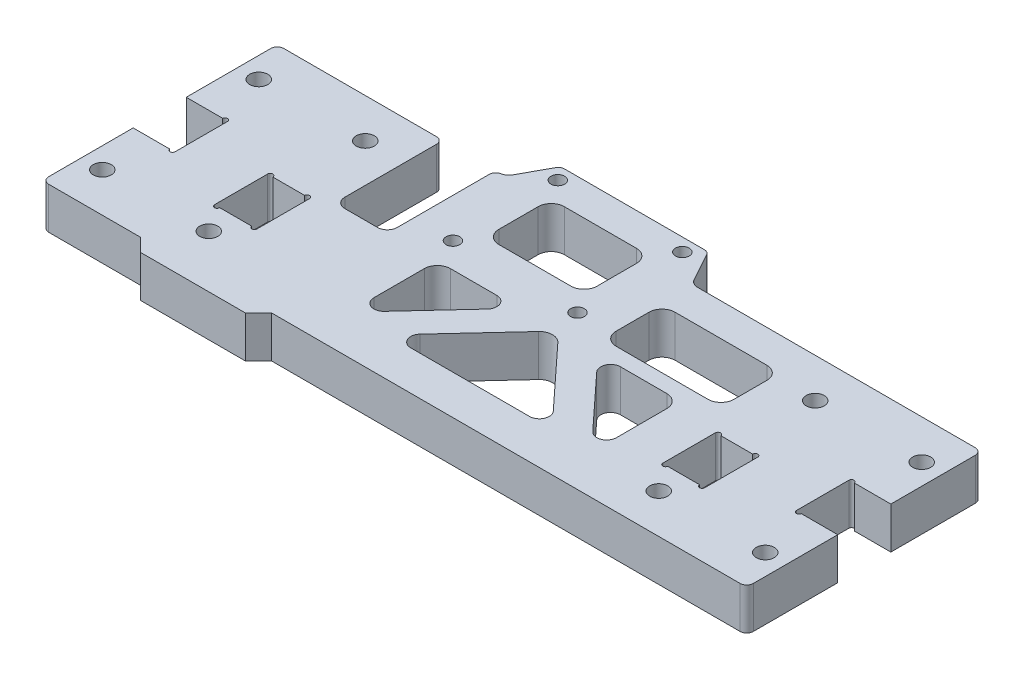
SolidWorks part; units mm, degrees
material "6061 Alloy"
ref_plane "Front Plane" through (0, 0, 0) normal (0, 0, 1) x (1, 0, 0)
ref_plane "Top Plane" through (0, 0, 0) normal (0, 1, 0) x (1, 0, 0)
ref_plane "Right Plane" through (0, 0, 0) normal (1, 0, 0) x (0, 0, -1)
sketch "Sketch1" plane through (0, 0, 0) normal (0, 1, 0) x (1, 0, 0)
  line L0 (107.5, 76.65) -> (107.5, 0) construction
  line L6 (32.7004, 36.1) -> (32.7004, 19.9)
  line L8 (45.6, 36) -> (45.6, 20)
  line L13 (0, 71.75) -> (69.5, 71.75)
  line L14 (69.5, 71.75) -> (75.5, 82.75)
  line L15 (75.5, 82.75) -> (120.5, 82.75)
  line L16 (120.5, 82.75) -> (126.5, 71.75)
  line L17 (126.5, 71.75) -> (215, 71.75)
  line L18 (32.7004, 28) -> (45.6, 28) construction
  line L19 (34.3004, 36.1) -> (44.0063, 36.1)
  line L20 (34.3004, 19.9) -> (44.0063, 19.9)
  line L21 (182.2996, 36.1) -> (182.2996, 19.9)
  line L22 (180.6996, 36.1) -> (170.9937, 36.1)
  line L23 (169.4, 36) -> (169.4, 20)
  line L24 (180.6996, 19.9) -> (170.9937, 19.9)
  line L25 (12.7, 35.875) -> (0, 35.875) construction
  line L29 (12.7, 43.975) -> (12.7, 27.775)
  line L30 (11.1189, 43.975) -> (0, 43.975)
  line L31 (11.1189, 27.775) -> (0, 27.775)
  line L32 (0, 27.775) -> (0, 0)
  line L33 (0, 43.975) -> (0, 71.75)
  line L34 (202.3, 35.875) -> (215, 35.875) construction
  line L35 (215, 43.975) -> (215, 71.75)
  line L36 (215, 27.775) -> (215, 0)
  line L37 (203.8811, 27.775) -> (215, 27.775)
  line L38 (203.8811, 43.975) -> (215, 43.975)
  line L39 (202.3, 43.975) -> (202.3, 27.775)
  line L40 (0, 0) -> (30, 0)
  line L41 (30, 0) -> (34, -4)
  line L42 (34, -4) -> (66, -4)
  line L43 (66, -4) -> (70, 0)
  line L44 (70, 0) -> (215, 0)
  circle A0 centre (38.85, 59.75) radius 2.75
  circle A5 centre (38.85, 12) radius 2.75
  circle A6 centre (176.15, 59.75) radius 2.75
  circle A7 centre (176.15, 12) radius 2.75
  arc A8 (32.7004, 36.1) -> (34.3004, 36.1) centre (33.5004, 36.1) cw
  arc A9 (45.6, 36) -> (44.0063, 36.1) centre (44.8, 36) ccw
  arc A10 (32.7004, 19.9) -> (34.3004, 19.9) centre (33.5004, 19.9) ccw
  arc A11 (45.6, 20) -> (44.0063, 19.9) centre (44.8, 20) cw
  arc A12 (182.2996, 19.9) -> (180.6996, 19.9) centre (181.4996, 19.9) cw
  arc A13 (182.2996, 36.1) -> (180.6996, 36.1) centre (181.4996, 36.1) ccw
  arc A14 (169.4, 36) -> (170.9937, 36.1) centre (170.2, 36) cw
  arc A15 (169.4, 20) -> (170.9937, 19.9) centre (170.2, 20) ccw
  circle A16 centre (6.35, 12) radius 2.75
  circle A17 centre (6.35, 59.75) radius 2.75
  arc A18 (12.7, 27.775) -> (11.1189, 27.775) centre (11.9095, 27.8976) cw
  arc A19 (12.7, 43.975) -> (11.1189, 43.975) centre (11.9095, 43.8524) ccw
  arc A20 (202.3, 43.975) -> (203.8811, 43.975) centre (203.0905, 43.8524) cw
  arc A21 (202.3, 27.775) -> (203.8811, 27.775) centre (203.0905, 27.8976) ccw
  circle A22 centre (208.65, 59.75) radius 2.75
  circle A23 centre (208.65, 12) radius 2.75
  point P77 (35.0575, 0)
  point P78 (11.1189, 19.2219)
  dimension "D12" = 5.5
  dimension "D16" = 5.5
  dimension "D17" = 0.8
  dimension "D18" = 0.8
  dimension "D19" = 0.8
  dimension "D20" = 0.8
  dimension "D21" = 5.5
  dimension "D22" = 5.5
  dimension "D27" = 0.8
  dimension "D1" = 215
  dimension "D2" = 71.75
  dimension "D5" = 61.9
  dimension "D6" = 12.9
  dimension "D4" = 11
  dimension "D7" = 6
  dimension "D8" = 38
  dimension "D10" = 45
  dimension "D11" = 16.2
  dimension "D14" = 6
  dimension "D13" = 12
  dimension "D25" = 16.2
  dimension "D3" = 12
  dimension "D23" = 16.2
  dimension "D26" = 12.7
  dimension "D9" = 4
  dimension "D15" = 30
  dimension "D24" = 40
  dimension "D28" = 4
  dimension "D29" = 35.875
extrude "Boss-Extrude1" add sketch "Sketch1" along normal blind 12.7
sketch "Sketch2" plane through (0, 12.7, 0) normal (0, 1, 0) x (1, 0, 0)
  line L1 (50.6, 85.2461) -> (66.6, 85.2461)
  line L2 (50.6, 85.2461) -> (50.6, 38.75)
  line L3 (50.6, 38.75) -> (66.6, 38.75)
  line L4 (66.6, 85.2461) -> (66.6, 38.75)
  line L5 (45.6, 20) -> (45.6, 36) construction
  line L12 (69.5, 71.75) -> (0, 71.75) construction
  dimension "D1" = 5
  dimension "D2" = 16
  dimension "D3" = 33
extrude "Cut-Extrude1" cut sketch "Sketch2" against normal through all
sketch "Sketch3" plane through (0, 12.7, 0) normal (0, 1, 0) x (1, 0, 0)
  line L1 (66.6, 38.75) -> (66.6, 71.75) construction
  line L2 (120.5, 82.75) -> (75.5, 82.75) construction
  circle A0 centre (78.6, 78.75) radius 2.1
  circle A1 centre (78.6, 46.75) radius 2.1
  circle A2 centre (116.6, 78.75) radius 2.1
  circle A3 centre (116.6, 46.75) radius 2.1
  dimension "D2" = 4.2
  dimension "D5" = 4.2
  dimension "D8" = 32
  dimension "D1" = 4
  dimension "D3" = 12
  dimension "D4" = 32
  dimension "D7" = 38
  dimension "D6" = 2
extrude "Cut-Extrude2" cut sketch "Sketch3" against normal through all
sketch "Sketch5" plane through (0, 12.7, 0) normal (0, 1, 0) x (1, 0, 0)
  line L2 (86.8013, 17.6174) -> (101.935, 33.9618)
  line L3 (99.7337, 39) -> (85.6, 39)
  line L8 (81.6, 35) -> (81.6, 19.6556)
  line L12 (66.6, 38.75) -> (66.6, 71.75) construction
  line L13 (115.665, 35.8302) -> (98.265, 17.0382)
  line L14 (118.6, 39) -> (118.6, 12) construction
  line L15 (100.4663, 12) -> (136.7337, 12)
  line L16 (121.535, 35.8302) -> (138.935, 17.0382)
  line L17 (137.4663, 39) -> (151.6, 39)
  line L18 (150.3987, 17.6174) -> (135.265, 33.9618)
  line L19 (155.6, 35) -> (155.6, 19.6556)
  line L20 (120.5, 82.75) -> (75.5, 82.75) construction
  line L21 (86.6, 72.75) -> (108.6, 72.75)
  line L22 (82.6, 68.75) -> (82.6, 56.75)
  line L23 (86.6, 52.75) -> (108.6, 52.75)
  line L24 (112.6, 68.75) -> (112.6, 56.75)
  line L25 (215, 71.75) -> (126.5, 71.75) construction
  line L26 (131.4, 61.75) -> (159.4, 61.75)
  line L27 (127.4, 57.75) -> (127.4, 47.75)
  line L28 (131.4, 43.75) -> (159.4, 43.75)
  line L29 (163.4, 57.75) -> (163.4, 47.75)
  line L31 (169.4, 36) -> (169.4, 20) construction
  arc A0 (121.535, 35.8302) -> (115.665, 35.8302) centre (118.6, 33.1125) ccw
  arc A1 (155.6, 35) -> (151.6, 39) centre (151.6, 35) ccw
  arc A2 (81.6, 35) -> (85.6, 39) centre (85.6, 35) cw
  arc A3 (112.6, 68.75) -> (108.6, 72.75) centre (108.6, 68.75) ccw
  arc A4 (108.6, 52.75) -> (112.6, 56.75) centre (108.6, 56.75) ccw
  arc A5 (82.6, 56.75) -> (86.6, 52.75) centre (86.6, 56.75) ccw
  arc A6 (82.6, 68.75) -> (86.6, 72.75) centre (86.6, 68.75) cw
  arc A7 (150.3987, 17.6174) -> (155.6, 19.6556) centre (152.6, 19.6556) ccw
  arc A8 (135.265, 33.9618) -> (137.4663, 39) centre (137.4663, 36) cw
  arc A9 (86.8013, 17.6174) -> (81.6, 19.6556) centre (84.6, 19.6556) cw
  arc A10 (136.7337, 12) -> (138.935, 17.0382) centre (136.7337, 15) ccw
  arc A11 (100.4663, 12) -> (98.265, 17.0382) centre (100.4663, 15) cw
  arc A12 (101.935, 33.9618) -> (99.7337, 39) centre (99.7337, 36) ccw
  arc A13 (163.4, 57.75) -> (159.4, 61.75) centre (159.4, 57.75) ccw
  arc A14 (159.4, 43.75) -> (163.4, 47.75) centre (159.4, 47.75) ccw
  arc A15 (127.4, 47.75) -> (131.4, 43.75) centre (131.4, 47.75) ccw
  arc A16 (127.4, 57.75) -> (131.4, 61.75) centre (131.4, 57.75) cw
  point P25 (155.6, 39)
  point P28 (81.6, 39)
  point P33 (112.6, 52.75)
  point P36 (82.6, 52.75)
  point P39 (82.6, 72.75)
  point P42 (155.6, 12)
  point P45 (130.6, 39)
  point P48 (81.6, 12)
  point P51 (143.6, 12)
  point P54 (93.6, 12)
  point P57 (106.6, 39)
  point P68 (163.4, 61.75)
  point P71 (163.4, 43.75)
  point P76 (127.4, 61.75)
  point P77 (0, 0)
  dimension "D11" = 4
  dimension "D12" = 3
  dimension "D13" = 3
  dimension "D14" = 3
  dimension "D19" = 4
  dimension "D2" = 27
  dimension "D3" = 12
  dimension "D4" = 15
  dimension "D5" = 25
  dimension "D6" = 25
  dimension "D7" = 10
  dimension "D8" = 16
  dimension "D9" = 20
  dimension "D10" = 30
  dimension "D15" = 10
  dimension "D16" = 18
  dimension "D17" = 6
  dimension "D18" = 36
extrude "Cut-Extrude3" cut sketch "Sketch5" against normal through all
fillet "Fillet1" radius 3 4 edges at (69.5, 6.35, -71.75) (66.6, 6.35, -38.75) (50.6, 6.35, -38.75) (126.5, 6.35, -71.75)
fillet "Fillet2" radius 2 8 edges at (215, 6.35, -71.75) (120.5, 6.35, -82.75) (75.5, 6.35, -82.75) (50.6, 6.35, -71.75) (66.6, 6.35, -71.75) (0, 6.35, -71.75) (215, 6.35, 0) (0, 6.35, 0)
equation "\"DriveMotorLength\"= 90mm"
equation "\"DriveMotorGap\"= 10mm"
equation "\"AluminumThickness\"= 0.5in"
equation "\"ChassisWidth\"= ( \"DriveMotorLength\" + \"AluminumThickness\" ) * 2 + \"DriveMotorGap\""
equation "\"RepeatMagnumHoleWidth\"= 19.05mm"
equation "\"MortiseWidth\"= 16mm"
equation "\"ChassisScrewThruHole\"= 5.5mm"
equation "\"D11@Sketch1\"=\"MortiseSlotWidth\""
equation "\"D12@Sketch1\"=\"ChassisScrewThruHole\""
equation "\"D16@Sketch1\"=\"ChassisScrewThruHole\""
equation "\"MortiseSlotWidth\"= 16.2mm"
equation "\"Dogbone\"= 0.8mm"
equation "\"D17@Sketch1\"=\"Dogbone\""
equation "\"D18@Sketch1\"=\"Dogbone\""
equation "\"D19@Sketch1\"=\"Dogbone\""
equation "\"D20@Sketch1\"=\"Dogbone\""
equation "\"D21@Sketch1\"=\"ChassisScrewThruHole\""
equation "\"D22@Sketch1\"=\"ChassisScrewThruHole\""
equation "\"D27@Sketch1\"=\"Dogbone\""
equation "\"D23@Sketch1\"=\"MortiseSlotWidth\""
equation "\"D25@Sketch1\"=\"MortiseSlotWidth\""
